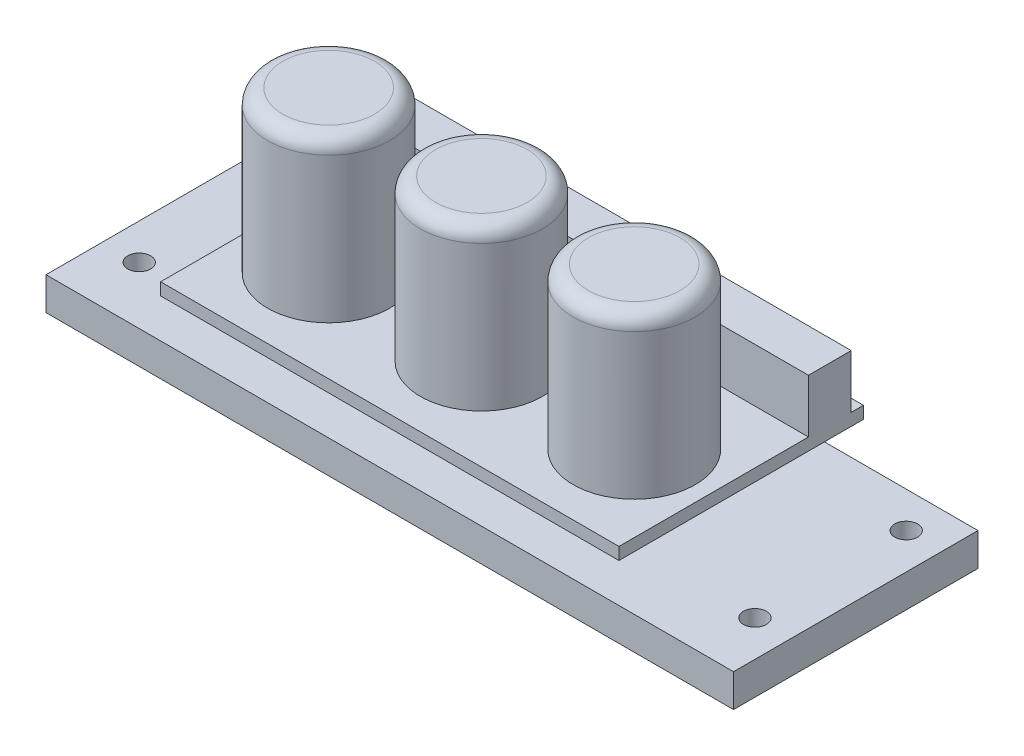
SolidWorks part; units mm, degrees
ref_plane "Front Plane" through (0, 0, 0) normal (0, 0, 1) x (1, 0, 0)
ref_plane "Top Plane" through (0, 0, 0) normal (0, 1, 0) x (1, 0, 0)
ref_plane "Right Plane" through (0, 0, 0) normal (1, 0, 0) x (0, 0, -1)
sketch "Sketch2" plane through (0, 0, 0) normal (0, 1, 0) x (1, 0, 0)
  line L0 (0, -55) -> (0, 55) construction
  line L1 (-45, -16) -> (45, -16)
  line L2 (-45, -16) -> (-45, 16)
  line L3 (-45, 16) -> (45, 16)
  line L4 (45, -16) -> (45, 16)
  line L5 (-45, -16) -> (45, 16) construction
  line L6 (-45, 16) -> (45, -16) construction
  circle A0 centre (40.3, 11.3) radius 1.5
  circle A1 centre (40.3, -8.5) radius 1.5
  circle A2 centre (-40.3, -8.5) radius 1.5
  circle A3 centre (-40.3, 11.3) radius 1.5
  point P0 (0, 0)
  point P10 (40.3, -8.2562)
  dimension "D3" = 3
  dimension "D1" = 90
  dimension "D2" = 32
  dimension "D4" = 4.7
  dimension "D5" = 4.7
  dimension "D6" = 19.8
extrude "Boss-Extrude1" add sketch "Sketch2" along normal blind 4.3
ref_plane "Plane1" through (0, 9.4, 0) normal (0, 1, 0) x (1, 0, 0)
sketch "Sketch3" plane through (0, 9.4, 0) normal (0, 1, 0) x (1, 0, 0)
  line L0 (45, 16) -> (-45, 16) construction
  line L1 (-30, -16) -> (30, -16)
  line L2 (-30, -16) -> (-30, 16)
  line L3 (-30, 16) -> (30, 16)
  line L4 (30, -16) -> (30, 16)
  line L5 (-30, -16) -> (30, 16) construction
  line L6 (-30, 16) -> (30, -16) construction
  point P0 (0, 0)
  dimension "D1" = 60
extrude "Boss-Extrude2" add sketch "Sketch3" along normal blind 1.6 separate body
sketch "Sketch4" plane through (0, 11, 0) normal (0, 1, 0) x (1, 0, 0)
  line L1 (-30, -16) -> (30, -16) construction
  line L2 (0, -6.05) -> (0, 6.05) construction
  circle A0 centre (20, -4) radius 8
  circle A1 centre (0, -4) radius 8
  circle A2 centre (-20, -4) radius 8
  dimension "D1" = 16
  dimension "D4" = 16
  dimension "D2" = 12
  dimension "D3" = 20
extrude "Boss-Extrude3" add sketch "Sketch4" along normal blind 21
fillet "Fillet1" radius 2 3 edges at (-20, 32, -4) (20, 32, 12) (0, 32, 12)
sketch "Sketch5" plane through (0, 0, 0) normal (1, 0, 0) x (0, 0, -1)
  line L5 (14.4072, 11) -> (8.8072, 11)
  line L6 (14.4072, 11) -> (14.4072, 18)
  line L7 (8.8072, 11) -> (8.8072, 18)
  line L8 (14.4072, 18) -> (8.8072, 18)
  line L9 (-16, 11) -> (16, 11) construction
  dimension "D1" = 5.6
  dimension "D2" = 7
extrude "Boss-Extrude4" add sketch "Sketch5" along normal blind 30 and the other way blind 30 contours L6 L8 L7 L5
